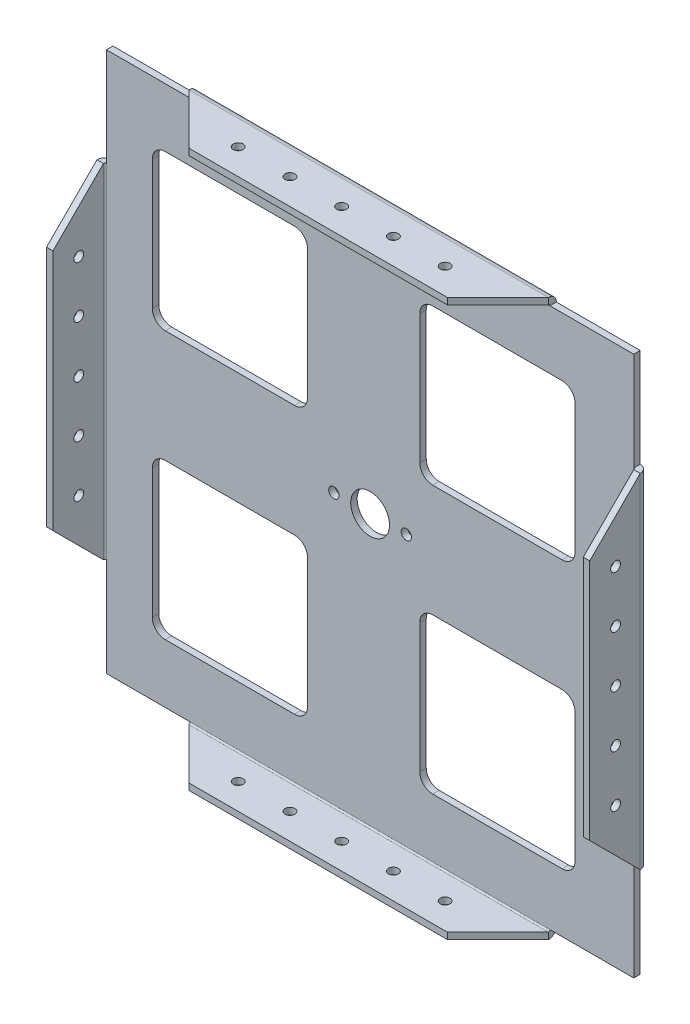
SolidWorks part; units mm, degrees
note: The reader was unsure of these and kept them because the rebuilt part matched: flange length of "Edge-Flange13", "Edge-Flange14", "Edge-Flange15", "Edge-Flange16".
ref_plane "Front Plane" through (0, 0, 0) normal (0, 0, 1) x (1, 0, 0)
ref_plane "Top Plane" through (0, 0, 0) normal (0, 1, 0) x (1, 0, 0)
ref_plane "Right Plane" through (0, 0, 0) normal (1, 0, 0) x (0, 0, -1)
sketch "Sketch1" plane through (0, 0, 0) normal (0, 0, 1) x (1, 0, 0)
  line L1 (-132.2122, 105.5541) -> (134.4878, 105.5541)
  line L2 (-132.2122, 105.5541) -> (-132.2122, -167.4959)
  line L3 (-132.2122, -167.4959) -> (134.4878, -167.4959)
  line L4 (134.4878, 105.5541) -> (134.4878, -167.4959)
  line L5 (-99.4462, 72.7881) -> (-35.9462, 72.7881)
  line L6 (-105.7962, 66.4381) -> (-105.7962, 2.9381)
  line L7 (-99.4462, -3.4119) -> (-35.9462, -3.4119)
  line L8 (-29.5962, 66.4381) -> (-29.5962, 2.9381)
  line L9 (31.8718, 72.7881) -> (95.3718, 72.7881)
  line L10 (25.5218, 66.4381) -> (25.5218, 2.9381)
  line L11 (31.8718, -3.4119) -> (95.3718, -3.4119)
  line L12 (101.7218, 66.4381) -> (101.7218, 2.9381)
  line L13 (-99.4462, -58.5299) -> (-35.9462, -58.5299)
  line L14 (-105.7962, -64.8799) -> (-105.7962, -128.3799)
  line L15 (-99.4462, -134.7299) -> (-35.9462, -134.7299)
  line L16 (-29.5962, -64.8799) -> (-29.5962, -128.3799)
  line L17 (31.8718, -58.5299) -> (95.3718, -58.5299)
  line L18 (25.5218, -64.8799) -> (25.5218, -128.3799)
  line L19 (31.8718, -134.7299) -> (95.3718, -134.7299)
  line L20 (101.7218, -64.8799) -> (101.7218, -128.3799)
  arc A0 (-35.9462, -58.5299) -> (-29.5962, -64.8799) centre (-35.9462, -64.8799) cw
  arc A1 (-29.5962, -128.3799) -> (-35.9462, -134.7299) centre (-35.9462, -128.3799) cw
  arc A2 (-99.4462, -134.7299) -> (-105.7962, -128.3799) centre (-99.4462, -128.3799) cw
  arc A3 (-105.7962, -64.8799) -> (-99.4462, -58.5299) centre (-99.4462, -64.8799) cw
  arc A4 (101.7218, -64.8799) -> (95.3718, -58.5299) centre (95.3718, -64.8799) ccw
  arc A5 (95.3718, -134.7299) -> (101.7218, -128.3799) centre (95.3718, -128.3799) ccw
  arc A6 (31.8718, -134.7299) -> (25.5218, -128.3799) centre (31.8718, -128.3799) cw
  arc A7 (25.5218, -64.8799) -> (31.8718, -58.5299) centre (31.8718, -64.8799) cw
  arc A8 (101.7218, 66.4381) -> (95.3718, 72.7881) centre (95.3718, 66.4381) ccw
  arc A9 (31.8718, -3.4119) -> (25.5218, 2.9381) centre (31.8718, 2.9381) cw
  arc A10 (31.8718, 72.7881) -> (25.5218, 66.4381) centre (31.8718, 66.4381) ccw
  arc A11 (101.7218, 2.9381) -> (95.3718, -3.4119) centre (95.3718, 2.9381) cw
  arc A12 (-29.5962, 2.9381) -> (-35.9462, -3.4119) centre (-35.9462, 2.9381) cw
  arc A13 (-35.9462, 72.7881) -> (-29.5962, 66.4381) centre (-35.9462, 66.4381) cw
  arc A14 (-99.4462, -3.4119) -> (-105.7962, 2.9381) centre (-99.4462, 2.9381) cw
  arc A15 (-105.7962, 66.4381) -> (-99.4462, 72.7881) centre (-99.4462, 66.4381) cw
  circle A16 centre (1.1378, -30.9709) radius 9.525
  circle A17 centre (-16.6422, -30.8439) radius 2.54
  circle A18 centre (18.9174, -30.8439) radius 2.54
  point P24 (-29.5962, -134.7299)
  point P27 (-105.7962, -134.7299)
  point P30 (-105.7962, -58.5299)
  point P33 (101.7218, -58.5299)
  point P36 (101.7218, -134.7299)
  point P39 (25.5218, -134.7299)
  point P44 (101.7218, 72.7881)
  point P49 (25.5218, 72.7881)
  point P52 (101.7218, -3.4119)
  point P57 (-29.5962, 72.7881)
  point P60 (-105.7962, -3.4119)
  point P63 (-105.7962, 72.7881)
  dimension "D19" = 6.35
  dimension "D20" = 19.05
  dimension "D23" = 5.08
  dimension "D24" = 5.08
  dimension "D1" = 266.7
  dimension "D2" = 273.05
  dimension "D3" = 76.2
  dimension "D4" = 76.2
  dimension "D5" = 76.2
  dimension "D6" = 76.2
  dimension "D7" = 76.2
  dimension "D8" = 76.2
  dimension "D9" = 76.2
  dimension "D10" = 76.2
  dimension "D11" = 32.766
  dimension "D12" = 32.766
  dimension "D13" = 32.766
  dimension "D14" = 32.766
  dimension "D15" = 32.766
  dimension "D16" = 32.766
  dimension "D17" = 26.416
  dimension "D18" = 26.416
  dimension "D21" = 136.525
  dimension "D22" = 133.35
  dimension "D25" = 17.78
  dimension "D26" = 17.78
  dimension "D27" = 27.432
  dimension "D28" = 27.432
base flange "Base-Flange4" sketch "Sketch1" thickness 3.175 reverse thickness direction no parameters "D1"=0.7366
edge flange "Edge-Flange13" sketch "Sketch93" flange angle 90 flange length 28.702 flange position material inside bend radius 0.7366 thickness 3.175 relief rectangular parameters "D6"=10
sketch "Sketch93" plane through (0, -167.4959, 0) normal (0, 1, 0) x (-1, 0, 0)
  line L1 (132.2122, 0) -> (-134.4878, 0) construction
  line L2 (-134.4878, 0) -> (-134.4878, 25.527)
  line L3 (-134.4878, 25.527) -> (132.2122, 25.527)
  line L4 (132.2122, 25.527) -> (132.2122, 0)
  line L5 (132.2122, 0) -> (-134.4878, 0)
bend "EdgeBend13" bend radius 0.7366 bend angle 90 parameters "D5"=1
edge flange "Edge-Flange14" sketch "Sketch96" flange angle 90 flange length 28.702 flange position material inside bend radius 0.7366 thickness 3.175 relief rectangular parameters "D6"=10
sketch "Sketch96" plane through (0, 105.5541, 0) normal (0, -1, 0) x (1, 0, 0)
  line L1 (134.4878, 0) -> (-132.2122, 0) construction
  line L2 (-132.2122, 0) -> (-132.2122, 25.527)
  line L3 (-132.2122, 25.527) -> (134.4878, 25.527)
  line L4 (134.4878, 25.527) -> (134.4878, 0)
  line L5 (134.4878, 0) -> (-132.2122, 0)
bend "EdgeBend14" bend radius 0.7366 bend angle 90 parameters "D5"=2
sketch "Sketch97" plane through (0, -164.3209, 0) normal (0, 1, 0) x (1, 0, 0)
  line L0 (-132.2122, -0.7366) -> (134.4878, -0.7366) construction
  line L1 (134.4878, -25.527) -> (90.0378, -25.527)
  line L2 (134.4878, -25.527) -> (134.4878, -0.7366)
  line L3 (134.4878, -0.7366) -> (90.0378, -0.7366)
  line L4 (90.0378, -25.527) -> (90.0378, -0.7366)
  dimension "D1" = 44.45
extrude "Cut-Extrude17" cut sketch "Sketch97" against normal blind 47.752 normal cut yes
sketch "Sketch98" plane through (0, -164.3209, 0) normal (0, 1, 0) x (1, 0, 0)
  line L0 (-132.2122, -0.7366) -> (90.0378, -0.7366) construction
  line L1 (-132.2122, -25.527) -> (-87.7622, -25.527)
  line L2 (-132.2122, -25.527) -> (-132.2122, -0.7366)
  line L3 (-132.2122, -0.7366) -> (-87.7622, -0.7366)
  line L4 (-87.7622, -25.527) -> (-87.7622, -0.7366)
  dimension "D1" = 44.45
extrude "Cut-Extrude18" cut sketch "Sketch98" against normal blind 47.752 normal cut yes
sketch "Sketch99" plane through (0, 105.5541, 0) normal (0, 1, 0) x (1, 0, 0)
  line L0 (134.4878, -0.7366) -> (-132.2122, -0.7366) construction
  line L1 (134.4878, -25.527) -> (90.0378, -25.527)
  line L2 (134.4878, -25.527) -> (134.4878, -0.7366)
  line L3 (134.4878, -0.7366) -> (90.0378, -0.7366)
  line L4 (90.0378, -25.527) -> (90.0378, -0.7366)
  dimension "D1" = 44.45
extrude "Cut-Extrude19" cut sketch "Sketch99" against normal blind 47.752 normal cut yes
sketch "Sketch100" plane through (0, 105.5541, 0) normal (0, 1, 0) x (1, 0, 0)
  line L0 (90.0378, -25.527) -> (-132.2122, -25.527) construction
  line L1 (-132.2122, -0.7366) -> (-87.7622, -0.7366)
  line L2 (-132.2122, -0.7366) -> (-132.2122, -25.527)
  line L3 (-132.2122, -25.527) -> (-87.7622, -25.527)
  line L4 (-87.7622, -0.7366) -> (-87.7622, -25.527)
  dimension "D1" = 44.45
extrude "Cut-Extrude20" cut sketch "Sketch100" against normal blind 47.752 normal cut yes
edge flange "Edge-Flange15" sketch "Sketch103" flange angle 90 flange length 28.702 flange position material inside bend radius 0.7366 thickness 3.175 relief none parameters "D6"=10
sketch "Sketch103" plane through (134.4878, 0, 0) normal (-1, 0, 0) x (0, -1, 0)
  line L1 (163.5843, 0) -> (-101.6425, 0) construction
  line L2 (-101.6425, 0) -> (-101.6425, 25.527)
  line L3 (-101.6425, 25.527) -> (163.5843, 25.527)
  line L4 (163.5843, 25.527) -> (163.5843, 0)
  line L5 (163.5843, 0) -> (-101.6425, 0)
bend "EdgeBend15" bend radius 0.7366 bend angle 90 parameters "D5"=3
edge flange "Edge-Flange16" sketch "Sketch106" flange angle 90 flange length 28.702 flange position material inside bend radius 0.7366 thickness 3.175 relief none parameters "D6"=10
sketch "Sketch106" plane through (-132.2122, 0, 0) normal (1, 0, 0) x (0, 1, 0)
  line L1 (101.6425, 0) -> (-163.5843, 0) construction
  line L2 (-163.5843, 0) -> (-163.5843, 25.527)
  line L3 (-163.5843, 25.527) -> (101.6425, 25.527)
  line L4 (101.6425, 25.527) -> (101.6425, 0)
  line L5 (101.6425, 0) -> (-163.5843, 0)
bend "EdgeBend16" bend radius 0.7366 bend angle 90 parameters "D5"=4
sketch "Sketch107" plane through (-132.2122, 0, 0) normal (-1, 0, 0) x (0, 0, 1)
  line L0 (0.7366, 101.6425) -> (0.7366, -163.5843) construction
  line L1 (25.527, 101.6425) -> (0.7366, 101.6425)
  line L2 (25.527, 101.6425) -> (25.527, 53.8905)
  line L3 (25.527, 53.8905) -> (0.7366, 53.8905)
  line L4 (0.7366, 101.6425) -> (0.7366, 53.8905)
  dimension "D1" = 47.752
extrude "Cut-Extrude21" cut sketch "Sketch107" against normal blind 47.752 normal cut yes
sketch "Sketch108" plane through (-132.2122, 0, 0) normal (-1, 0, 0) x (0, 0, 1)
  line L0 (0.7366, 53.8905) -> (0.7366, -163.5843) construction
  line L1 (25.527, -163.5843) -> (0.7366, -163.5843)
  line L2 (25.527, -163.5843) -> (25.527, -115.8323)
  line L3 (25.527, -115.8323) -> (0.7366, -115.8323)
  line L4 (0.7366, -163.5843) -> (0.7366, -115.8323)
  dimension "D1" = 47.752
extrude "Cut-Extrude22" cut sketch "Sketch108" against normal blind 47.752 normal cut yes
sketch "Sketch109" plane through (134.4878, 0, 0) normal (1, 0, 0) x (0, 0, -1)
  line L0 (-0.7366, -163.5843) -> (-0.7366, 101.6425) construction
  line L1 (-25.527, -163.5843) -> (-0.7366, -163.5843)
  line L2 (-25.527, -163.5843) -> (-25.527, -115.8323)
  line L3 (-25.527, -115.8323) -> (-0.7366, -115.8323)
  line L4 (-0.7366, -163.5843) -> (-0.7366, -115.8323)
  dimension "D1" = 47.752
extrude "Cut-Extrude23" cut sketch "Sketch109" against normal blind 47.752 normal cut yes
sketch "Sketch110" plane through (134.4878, 0, 0) normal (1, 0, 0) x (0, 0, -1)
  line L0 (-0.7366, -115.8323) -> (-0.7366, 101.6425) construction
  line L1 (-25.527, 101.6425) -> (-0.7366, 101.6425)
  line L2 (-25.527, 101.6425) -> (-25.527, 53.8905)
  line L3 (-25.527, 53.8905) -> (-0.7366, 53.8905)
  line L4 (-0.7366, 101.6425) -> (-0.7366, 53.8905)
  dimension "D1" = 47.752
extrude "Cut-Extrude24" cut sketch "Sketch110" against normal blind 47.752 normal cut yes
chamfer "Chamfer5" distance 25.4 angle 45 8 edges at (90.0378, -165.9084, 25.527) (132.9003, -115.8323, 25.527) (-87.7622, -165.9084, 25.527) (-130.6247, -115.8323, 25.527) (-130.6247, 53.8905, 25.527) (-87.7622, 103.9666, 25.527) (132.9003, 53.8905, 25.527) (90.0378, 103.9666, 25.527)
sketch "Sketch113" plane through (0, 105.5541, 0) normal (0, 1, 0) x (1, 0, 0)
  line L0 (64.6378, -25.527) -> (-62.3622, -25.527) construction
  circle A0 centre (50.8, -12.827) radius 2.413
  circle A1 centre (25.4, -12.827) radius 2.413
  circle A2 centre (0, -12.827) radius 2.413
  circle A3 centre (-25.4, -12.827) radius 2.413
  circle A4 centre (-50.8, -12.827) radius 2.413
  dimension "D1" = 4.826
  dimension "D2" = 4.826
  dimension "D3" = 4.826
  dimension "D4" = 4.826
  dimension "D5" = 4.826
  dimension "D6" = 12.7
  dimension "D7" = 25.4
  dimension "D8" = 25.4
  dimension "D9" = 25.4
  dimension "D10" = 25.4
extrude "Cut-Extrude25" cut sketch "Sketch113" against normal through all normal cut yes
sketch "Sketch114" plane through (134.4878, 0, 0) normal (1, 0, 0) x (0, 0, -1)
  line L1 (-25.527, -90.4323) -> (-25.527, 28.4905) construction
  circle A0 centre (-12.827, -81.8471) radius 2.413
  circle A1 centre (-12.827, -56.4471) radius 2.413
  circle A2 centre (-12.827, -31.0471) radius 2.413
  circle A3 centre (-12.827, -5.6471) radius 2.413
  circle A4 centre (-12.827, 19.7529) radius 2.413
  point P10 (-25.527, -30.9709)
  dimension "D1" = 4.826
  dimension "D2" = 4.826
  dimension "D3" = 4.826
  dimension "D4" = 4.826
  dimension "D5" = 4.826
  dimension "D6" = 136.4488
  dimension "D7" = 25.4
  dimension "D8" = 25.4
  dimension "D9" = 25.4
  dimension "D10" = 25.4
  dimension "D11" = 12.7
extrude "Cut-Extrude26" cut sketch "Sketch114" against normal through all normal cut yes
sketch "Sketch115" plane through (134.4878, 0, 0) normal (1, 0, 0) x (0, 0, -1)
  line L0 (-0.7366, -167.4959) -> (-0.7366, -164.3209)
  line L1 (0, -163.5843) -> (3.175, -163.5843)
  arc A0 (-0.7366, -167.4959) -> (3.175, -163.5843) centre (-0.7366, -163.5843) ccw
  arc A1 (-0.7366, -164.3209) -> (0, -163.5843) centre (-0.7366, -163.5843) ccw
extrude "Cut-Extrude28" cut sketch "Sketch115" against normal blind 45.0596 normal cut yes
sketch "Sketch116" plane through (-132.2122, 0, 0) normal (-1, 0, 0) x (0, 0, 1)
  line L0 (0, -163.5843) -> (-3.175, -163.5843)
  line L1 (0.7366, -164.3209) -> (0.7366, -167.4959)
  arc A0 (0, -163.5843) -> (0.7366, -164.3209) centre (0.7366, -163.5843) ccw
  arc A1 (-3.175, -163.5843) -> (0.7366, -167.4959) centre (0.7366, -163.5843) ccw
extrude "Cut-Extrude29" cut sketch "Sketch116" against normal blind 45.0596 normal cut yes
sketch "Sketch117" plane through (0, -163.5843, 0) normal (0, -1, 0) x (1, 0, 0)
  line L0 (-129.0372, 0.7366) -> (-132.2122, 0.7366)
  line L1 (-128.3006, 0) -> (-128.3006, -3.175)
  arc A0 (-132.2122, 0.7366) -> (-128.3006, -3.175) centre (-128.3006, 0.7366) ccw
  arc A1 (-129.0372, 0.7366) -> (-128.3006, 0) centre (-128.3006, 0.7366) ccw
extrude "Cut-Extrude30" cut sketch "Sketch117" against normal blind 48.3616 normal cut yes
sketch "Sketch118" plane through (134.4878, 0, 0) normal (1, 0, 0) x (0, 0, -1)
  line L0 (-0.7366, 102.3791) -> (-0.7366, 105.5541)
  line L1 (0, 101.6425) -> (3.175, 101.6425)
  arc A0 (0, 101.6425) -> (-0.7366, 102.3791) centre (-0.7366, 101.6425) ccw
  arc A1 (3.175, 101.6425) -> (-0.7366, 105.5541) centre (-0.7366, 101.6425) ccw
extrude "Cut-Extrude31" cut sketch "Sketch118" against normal blind 45.0596 normal cut yes
sketch "Sketch119" plane through (-132.2122, 0, 0) normal (-1, 0, 0) x (0, 0, 1)
  line L0 (0.7366, 102.3791) -> (0.7366, 105.5541)
  line L1 (0, 101.6425) -> (-3.175, 101.6425)
  arc A0 (0.7366, 102.3791) -> (0, 101.6425) centre (0.7366, 101.6425) ccw
  arc A1 (0.7366, 105.5541) -> (-3.175, 101.6425) centre (0.7366, 101.6425) ccw
extrude "Cut-Extrude32" cut sketch "Sketch119" against normal blind 45.0596 normal cut yes
sketch "Sketch120" plane through (0, 101.6425, 0) normal (0, 1, 0) x (1, 0, 0)
  line L0 (-129.0372, -0.7366) -> (-132.2122, -0.7366)
  line L1 (-128.3006, 0) -> (-128.3006, 3.175)
  arc A0 (-128.3006, 0) -> (-129.0372, -0.7366) centre (-128.3006, -0.7366) ccw
  arc A1 (-128.3006, 3.175) -> (-132.2122, -0.7366) centre (-128.3006, -0.7366) ccw
extrude "Cut-Extrude33" cut sketch "Sketch120" against normal blind 48.3616 normal cut yes
sketch "Sketch121" plane through (0, -163.5843, 0) normal (0, -1, 0) x (1, 0, 0)
  line L0 (131.3128, 0.7366) -> (134.4878, 0.7366)
  line L1 (130.5762, 0) -> (130.5762, -3.175)
  arc A0 (130.5762, 0) -> (131.3128, 0.7366) centre (130.5762, 0.7366) ccw
  arc A1 (130.5762, -3.175) -> (134.4878, 0.7366) centre (130.5762, 0.7366) ccw
extrude "Cut-Extrude34" cut sketch "Sketch121" against normal blind 48.3616 normal cut yes
sketch "Sketch122" plane through (0, 101.6425, 0) normal (0, 1, 0) x (1, 0, 0)
  line L0 (134.4878, -0.7366) -> (131.3128, -0.7366)
  line L1 (130.5762, 0) -> (130.5762, 3.175)
  arc A0 (131.3128, -0.7366) -> (130.5762, 0) centre (130.5762, -0.7366) ccw
  arc A1 (134.4878, -0.7366) -> (130.5762, 3.175) centre (130.5762, -0.7366) ccw
extrude "Cut-Extrude35" cut sketch "Sketch122" against normal blind 48.3616 normal cut yes
sketch "Bend-Lines7" [suppressed] plane through (0, 0, 0) normal (0, 1, 0) x (1, 0, 0)
sketch "Bounding-Box7" [suppressed] plane through (0, 0, 0) normal (0, 1, 0) x (1, 0, 0)
sheet metal parameters "Sheet-Metal4" thickness 3.175 parameters "D1"=0.7366
flat pattern "Flat-Pattern4" [suppressed]
sketch "Bend-Lines8" plane through (0, 0, 0) normal (0, 1, 0) x (1, 0, 0)
sketch3d "Bounding-Box8" [suppressed]
  line L0 (134.4878, 105.5541, 0) -> (134.4878, -167.4959, 0) construction
  line L1 (-132.2122, 105.5541, 0) -> (-132.2122, -167.4959, 0) construction
  line L2 (134.4878, 105.5541, 0) -> (-132.2122, 105.5541, 0) construction
  line L3 (134.4878, -167.4959, 0) -> (-132.2122, -167.4959, 0) construction
sheet metal parameters "Sheet-Metal32" thickness 3.175 parameters "D1"=0.7366
flat pattern "Flat-Pattern4"
sketch "Bend-Lines8" plane through (0, 0, 0) normal (0, 0, 1) x (1, 0, 0)
  line L0 (-132.2122, -164.9857) -> (134.4878, -164.9857) construction
  line L1 (-132.2122, -164.9857) -> (134.4878, -164.9857) construction
sketch3d "Bounding-Box8" [suppressed]
  line L0 (134.4878, 105.5541, 0) -> (134.4878, -191.1776, 0) construction
  line L1 (-132.2122, 105.5541, 0) -> (-132.2122, -191.1776, 0) construction
  line L2 (134.4878, 105.5541, 0) -> (-132.2122, 105.5541, 0) construction
  line L3 (134.4878, -191.1776, 0) -> (-132.2122, -191.1776, 0) construction
bend of the flat pattern "Flatten-<EdgeBend13>1"
sheet metal parameters "Sheet-Metal33" thickness 3.175 parameters "D1"=0.7366
flat pattern "Flat-Pattern4"
sketch "Bend-Lines8" plane through (0, 0, 0) normal (0, 0, 1) x (1, 0, 0)
  line L0 (-132.2122, -164.9857) -> (134.4878, -164.9857) construction
  line L1 (-132.2122, -164.9857) -> (134.4878, -164.9857) construction
  line L2 (134.4878, 103.0439) -> (-132.2122, 103.0439) construction
  line L3 (134.4878, 103.0439) -> (-132.2122, 103.0439) construction
sketch3d "Bounding-Box8" [suppressed]
  line L0 (134.4878, 129.2357, 0) -> (134.4878, -191.1776, 0) construction
  line L1 (-132.2122, 129.2357, 0) -> (-132.2122, -191.1776, 0) construction
  line L2 (134.4878, 129.2357, 0) -> (-132.2122, 129.2357, 0) construction
  line L3 (134.4878, -191.1776, 0) -> (-132.2122, -191.1776, 0) construction
bend of the flat pattern "Flatten-<EdgeBend13>1"
bend of the flat pattern "Flatten-<EdgeBend14>1"
sheet metal parameters "Sheet-Metal34" thickness 3.175 parameters "D1"=0.7366
flat pattern "Flat-Pattern4"
sketch "Bend-Lines8" plane through (0, 0, 0) normal (0, 0, 1) x (1, 0, 0)
  line L0 (134.4878, -164.9857) -> (-132.2122, -164.9857) construction
  line L1 (134.4878, -164.9857) -> (-132.2122, -164.9857) construction
  line L2 (134.4878, 103.0439) -> (-132.2122, 103.0439) construction
  line L3 (134.4878, 103.0439) -> (-132.2122, 103.0439) construction
sketch3d "Bounding-Box8" [suppressed]
  line L0 (134.4878, 129.2357, 0) -> (134.4878, -191.1776, 0) construction
  line L1 (-132.2122, 129.2357, 0) -> (-132.2122, -191.1776, 0) construction
  line L2 (134.4878, 129.2357, 0) -> (-132.2122, 129.2357, 0) construction
  line L3 (134.4878, -191.1776, 0) -> (-132.2122, -191.1776, 0) construction
bend of the flat pattern "Flatten-<EdgeBend13>1"
bend of the flat pattern "Flatten-<EdgeBend14>1"
sheet metal parameters "Sheet-Metal35" thickness 3.175 parameters "D1"=0.7366
flat pattern "Flat-Pattern4"
sketch "Bend-Lines8" plane through (0, 0, 0) normal (0, 0, 1) x (1, 0, 0)
  line L0 (134.4878, -164.9857) -> (-132.2122, -164.9857) construction
  line L1 (134.4878, -164.9857) -> (-132.2122, -164.9857) construction
  line L2 (134.4878, 103.0439) -> (-132.2122, 103.0439) construction
  line L3 (134.4878, 103.0439) -> (-132.2122, 103.0439) construction
sketch3d "Bounding-Box8" [suppressed]
  line L0 (134.4878, 129.2357, 0) -> (134.4878, -191.1776, 0) construction
  line L1 (-132.2122, 129.2357, 0) -> (-132.2122, -191.1776, 0) construction
  line L2 (134.4878, 129.2357, 0) -> (-132.2122, 129.2357, 0) construction
  line L3 (134.4878, -191.1776, 0) -> (-132.2122, -191.1776, 0) construction
bend of the flat pattern "Flatten-<EdgeBend13>1"
bend of the flat pattern "Flatten-<EdgeBend14>1"
sheet metal parameters "Sheet-Metal36" thickness 3.175 parameters "D1"=0.7366
flat pattern "Flat-Pattern4"
sketch "Bend-Lines8" plane through (0, 0, 0) normal (0, 0, 1) x (1, 0, 0)
  line L0 (134.4878, -164.9857) -> (-132.2122, -164.9857) construction
  line L1 (134.4878, -164.9857) -> (-132.2122, -164.9857) construction
  line L2 (134.4878, 103.0439) -> (-132.2122, 103.0439) construction
  line L3 (134.4878, 103.0439) -> (-132.2122, 103.0439) construction
sketch3d "Bounding-Box8" [suppressed]
  line L0 (134.4878, 129.2357, 0) -> (134.4878, -191.1776, 0) construction
  line L1 (-132.2122, 129.2357, 0) -> (-132.2122, -191.1776, 0) construction
  line L2 (134.4878, 129.2357, 0) -> (-132.2122, 129.2357, 0) construction
  line L3 (134.4878, -191.1776, 0) -> (-132.2122, -191.1776, 0) construction
bend of the flat pattern "Flatten-<EdgeBend13>1"
bend of the flat pattern "Flatten-<EdgeBend14>1"
sheet metal parameters "Sheet-Metal37" thickness 3.175 parameters "D1"=0.7366
flat pattern "Flat-Pattern4"
sketch "Bend-Lines8" plane through (0, 0, 0) normal (0, 0, 1) x (1, 0, 0)
  line L0 (134.4878, -164.9857) -> (-132.2122, -164.9857) construction
  line L1 (134.4878, -164.9857) -> (-132.2122, -164.9857) construction
  line L2 (-132.2122, 103.0439) -> (134.4878, 103.0439) construction
  line L3 (-132.2122, 103.0439) -> (134.4878, 103.0439) construction
sketch3d "Bounding-Box8" [suppressed]
  line L0 (134.4878, 129.2357, 0) -> (134.4878, -191.1776, 0) construction
  line L1 (-132.2122, 129.2357, 0) -> (-132.2122, -191.1776, 0) construction
  line L2 (134.4878, 129.2357, 0) -> (-132.2122, 129.2357, 0) construction
  line L3 (134.4878, -191.1776, 0) -> (-132.2122, -191.1776, 0) construction
bend of the flat pattern "Flatten-<EdgeBend13>1"
bend of the flat pattern "Flatten-<EdgeBend14>1"
sheet metal parameters "Sheet-Metal38" thickness 3.175 parameters "D1"=0.7366
flat pattern "Flat-Pattern4"
sketch "Bend-Lines8" plane through (0, 0, 0) normal (0, 0, 1) x (1, 0, 0)
  line L0 (134.4878, -164.9857) -> (-132.2122, -164.9857) construction
  line L1 (134.4878, -164.9857) -> (-132.2122, -164.9857) construction
  line L2 (-132.2122, 103.0439) -> (134.4878, 103.0439) construction
  line L3 (-132.2122, 103.0439) -> (134.4878, 103.0439) construction
  line L4 (131.9776, -163.5843) -> (131.9776, 101.6425) construction
  line L5 (131.9776, -163.5843) -> (131.9776, 101.6425) construction
sketch3d "Bounding-Box8" [suppressed]
  line L0 (158.1695, 129.2357, 0) -> (158.1695, -191.1776, 0) construction
  line L1 (-132.2122, 129.2357, 0) -> (-132.2122, -191.1776, 0) construction
  line L2 (158.1695, 129.2357, 0) -> (-132.2122, 129.2357, 0) construction
  line L3 (158.1695, -191.1776, 0) -> (-132.2122, -191.1776, 0) construction
bend of the flat pattern "Flatten-<EdgeBend13>1"
bend of the flat pattern "Flatten-<EdgeBend14>1"
bend of the flat pattern "Flatten-<EdgeBend15>1"
sheet metal parameters "Sheet-Metal39" thickness 3.175 parameters "D1"=0.7366
flat pattern "Flat-Pattern4"
sketch "Bend-Lines8" plane through (0, 0, 0) normal (0, 0, 1) x (1, 0, 0)
  line L0 (134.4878, -164.9857) -> (-132.2122, -164.9857) construction
  line L1 (134.4878, -164.9857) -> (-132.2122, -164.9857) construction
  line L2 (-132.2122, 103.0439) -> (134.4878, 103.0439) construction
  line L3 (-132.2122, 103.0439) -> (134.4878, 103.0439) construction
  line L4 (131.9776, -163.5843) -> (131.9776, 101.6425) construction
  line L5 (131.9776, -163.5843) -> (131.9776, 101.6425) construction
  line L6 (-129.702, 101.6425) -> (-129.702, -163.5843) construction
  line L7 (-129.702, 101.6425) -> (-129.702, -163.5843) construction
sketch3d "Bounding-Box8" [suppressed]
  line L0 (158.1695, 129.2357, 0) -> (158.1695, -191.1776, 0) construction
  line L1 (-155.8938, 129.2357, 0) -> (-155.8938, -191.1776, 0) construction
  line L2 (158.1695, 129.2357, 0) -> (-155.8938, 129.2357, 0) construction
  line L3 (158.1695, -191.1776, 0) -> (-155.8938, -191.1776, 0) construction
bend of the flat pattern "Flatten-<EdgeBend13>1"
bend of the flat pattern "Flatten-<EdgeBend14>1"
bend of the flat pattern "Flatten-<EdgeBend15>1"
bend of the flat pattern "Flatten-<EdgeBend16>1"
sheet metal parameters "Sheet-Metal40" thickness 3.175 parameters "D1"=0.7366
flat pattern "Flat-Pattern4"
sketch "Bend-Lines8" plane through (0, 0, 0) normal (0, 0, 1) x (1, 0, 0)
  line L0 (134.4878, -164.9857) -> (-132.2122, -164.9857) construction
  line L1 (134.4878, -164.9857) -> (-132.2122, -164.9857) construction
  line L2 (-132.2122, 103.0439) -> (134.4878, 103.0439) construction
  line L3 (-132.2122, 103.0439) -> (134.4878, 103.0439) construction
  line L4 (131.9776, -163.5843) -> (131.9776, 101.6425) construction
  line L5 (131.9776, -163.5843) -> (131.9776, 101.6425) construction
  line L6 (-129.702, 101.6425) -> (-129.702, -163.5843) construction
  line L7 (-129.702, 101.6425) -> (-129.702, -163.5843) construction
sketch3d "Bounding-Box8" [suppressed]
  line L0 (158.1695, 129.2357, 0) -> (158.1695, -191.1776, 0) construction
  line L1 (-155.8938, 129.2357, 0) -> (-155.8938, -191.1776, 0) construction
  line L2 (158.1695, 129.2357, 0) -> (-155.8938, 129.2357, 0) construction
  line L3 (158.1695, -191.1776, 0) -> (-155.8938, -191.1776, 0) construction
bend of the flat pattern "Flatten-<EdgeBend13>1"
bend of the flat pattern "Flatten-<EdgeBend14>1"
bend of the flat pattern "Flatten-<EdgeBend15>1"
bend of the flat pattern "Flatten-<EdgeBend16>1"
sheet metal parameters "Sheet-Metal41" thickness 3.175 parameters "D1"=0.7366
flat pattern "Flat-Pattern4"
sketch "Bend-Lines8" plane through (0, 0, 0) normal (0, 0, 1) x (1, 0, 0)
  line L0 (134.4878, -164.9857) -> (-132.2122, -164.9857) construction
  line L1 (134.4878, -164.9857) -> (-132.2122, -164.9857) construction
  line L2 (-132.2122, 103.0439) -> (134.4878, 103.0439) construction
  line L3 (-132.2122, 103.0439) -> (134.4878, 103.0439) construction
  line L4 (131.9776, -163.5843) -> (131.9776, 101.6425) construction
  line L5 (131.9776, -163.5843) -> (131.9776, 101.6425) construction
  line L6 (-129.702, -163.5843) -> (-129.702, 101.6425) construction
  line L7 (-129.702, -163.5843) -> (-129.702, 101.6425) construction
sketch3d "Bounding-Box8" [suppressed]
  line L0 (158.1695, 129.2357, 0) -> (158.1695, -191.1776, 0) construction
  line L1 (-155.8938, 129.2357, 0) -> (-155.8938, -191.1776, 0) construction
  line L2 (158.1695, 129.2357, 0) -> (-155.8938, 129.2357, 0) construction
  line L3 (158.1695, -191.1776, 0) -> (-155.8938, -191.1776, 0) construction
bend of the flat pattern "Flatten-<EdgeBend13>1"
bend of the flat pattern "Flatten-<EdgeBend14>1"
bend of the flat pattern "Flatten-<EdgeBend15>1"
bend of the flat pattern "Flatten-<EdgeBend16>1"
sheet metal parameters "Sheet-Metal42" thickness 3.175 parameters "D1"=0.7366
flat pattern "Flat-Pattern4"
sketch "Bend-Lines8" plane through (0, 0, 0) normal (0, 0, 1) x (1, 0, 0)
  line L0 (134.4878, -164.9857) -> (-132.2122, -164.9857) construction
  line L1 (134.4878, -164.9857) -> (-132.2122, -164.9857) construction
  line L2 (-132.2122, 103.0439) -> (134.4878, 103.0439) construction
  line L3 (-132.2122, 103.0439) -> (134.4878, 103.0439) construction
  line L4 (131.9776, -163.5843) -> (131.9776, 101.6425) construction
  line L5 (131.9776, -163.5843) -> (131.9776, 101.6425) construction
  line L6 (-129.702, -163.5843) -> (-129.702, 101.6425) construction
  line L7 (-129.702, -163.5843) -> (-129.702, 101.6425) construction
sketch3d "Bounding-Box8" [suppressed]
  line L0 (158.1695, 129.2357, 0) -> (158.1695, -191.1776, 0) construction
  line L1 (-155.8938, 129.2357, 0) -> (-155.8938, -191.1776, 0) construction
  line L2 (158.1695, 129.2357, 0) -> (-155.8938, 129.2357, 0) construction
  line L3 (158.1695, -191.1776, 0) -> (-155.8938, -191.1776, 0) construction
bend of the flat pattern "Flatten-<EdgeBend13>1"
bend of the flat pattern "Flatten-<EdgeBend14>1"
bend of the flat pattern "Flatten-<EdgeBend15>1"
bend of the flat pattern "Flatten-<EdgeBend16>1"
sheet metal parameters "Sheet-Metal43" thickness 3.175 parameters "D1"=0.7366
flat pattern "Flat-Pattern4"
sketch "Bend-Lines8" plane through (0, 0, 0) normal (0, 0, 1) x (1, 0, 0)
  line L0 (134.4878, -164.9857) -> (-132.2122, -164.9857) construction
  line L1 (134.4878, -164.9857) -> (-132.2122, -164.9857) construction
  line L2 (-132.2122, 103.0439) -> (134.4878, 103.0439) construction
  line L3 (-132.2122, 103.0439) -> (134.4878, 103.0439) construction
  line L4 (131.9776, 101.6425) -> (131.9776, -163.5843) construction
  line L5 (131.9776, 101.6425) -> (131.9776, -163.5843) construction
  line L6 (-129.702, -163.5843) -> (-129.702, 101.6425) construction
  line L7 (-129.702, -163.5843) -> (-129.702, 101.6425) construction
sketch3d "Bounding-Box8" [suppressed]
  line L0 (158.1695, 129.2357, 0) -> (158.1695, -191.1776, 0) construction
  line L1 (-155.8938, 129.2357, 0) -> (-155.8938, -191.1776, 0) construction
  line L2 (158.1695, 129.2357, 0) -> (-155.8938, 129.2357, 0) construction
  line L3 (158.1695, -191.1776, 0) -> (-155.8938, -191.1776, 0) construction
bend of the flat pattern "Flatten-<EdgeBend13>1"
bend of the flat pattern "Flatten-<EdgeBend14>1"
bend of the flat pattern "Flatten-<EdgeBend15>1"
bend of the flat pattern "Flatten-<EdgeBend16>1"
sheet metal parameters "Sheet-Metal44" thickness 3.175 parameters "D1"=0.7366
flat pattern "Flat-Pattern4"
sketch "Bend-Lines8" plane through (0, 0, 0) normal (0, 0, 1) x (1, 0, 0)
  line L0 (134.4878, -164.9857) -> (-132.2122, -164.9857) construction
  line L1 (134.4878, -164.9857) -> (-132.2122, -164.9857) construction
  line L2 (-132.2122, 103.0439) -> (134.4878, 103.0439) construction
  line L3 (-132.2122, 103.0439) -> (134.4878, 103.0439) construction
  line L4 (131.9776, 101.6425) -> (131.9776, -163.5843) construction
  line L5 (131.9776, 101.6425) -> (131.9776, -163.5843) construction
  line L6 (-129.702, -163.5843) -> (-129.702, 101.6425) construction
  line L7 (-129.702, -163.5843) -> (-129.702, 101.6425) construction
sketch3d "Bounding-Box8" [suppressed]
  line L0 (158.1695, 129.2357, 0) -> (158.1695, -191.1776, 0) construction
  line L1 (-155.8938, 129.2357, 0) -> (-155.8938, -191.1776, 0) construction
  line L2 (158.1695, 129.2357, 0) -> (-155.8938, 129.2357, 0) construction
  line L3 (158.1695, -191.1776, 0) -> (-155.8938, -191.1776, 0) construction
bend of the flat pattern "Flatten-<EdgeBend13>1"
bend of the flat pattern "Flatten-<EdgeBend14>1"
bend of the flat pattern "Flatten-<EdgeBend15>1"
bend of the flat pattern "Flatten-<EdgeBend16>1"
sheet metal parameters "Sheet-Metal45" thickness 3.175 parameters "D1"=0.7366
flat pattern "Flat-Pattern4"
sketch "Bend-Lines8" plane through (0, 0, 0) normal (0, 0, 1) x (1, 0, 0)
  line L0 (134.4878, -164.9857) -> (-132.2122, -164.9857) construction
  line L1 (134.4878, -164.9857) -> (-132.2122, -164.9857) construction
  line L2 (-132.2122, 103.0439) -> (134.4878, 103.0439) construction
  line L3 (-132.2122, 103.0439) -> (134.4878, 103.0439) construction
  line L4 (131.9776, 101.6425) -> (131.9776, -163.5843) construction
  line L5 (131.9776, 101.6425) -> (131.9776, -163.5843) construction
  line L6 (-129.702, -163.5843) -> (-129.702, 101.6425) construction
  line L7 (-129.702, -163.5843) -> (-129.702, 101.6425) construction
sketch3d "Bounding-Box8" [suppressed]
  line L0 (158.1695, 129.2357, 0) -> (158.1695, -191.1776, 0) construction
  line L1 (-155.8938, 129.2357, 0) -> (-155.8938, -191.1776, 0) construction
  line L2 (158.1695, 129.2357, 0) -> (-155.8938, 129.2357, 0) construction
  line L3 (158.1695, -191.1776, 0) -> (-155.8938, -191.1776, 0) construction
bend of the flat pattern "Flatten-<EdgeBend13>1"
bend of the flat pattern "Flatten-<EdgeBend14>1"
bend of the flat pattern "Flatten-<EdgeBend15>1"
bend of the flat pattern "Flatten-<EdgeBend16>1"
sheet metal parameters "Sheet-Metal47" thickness 3.175 parameters "D1"=0.7366
flat pattern "Flat-Pattern4"
sketch "Bend-Lines8" plane through (0, 0, 0) normal (0, 0, 1) x (1, 0, 0)
  line L0 (-132.2122, -164.9857) -> (89.4282, -164.9857) construction
  line L1 (-132.2122, -164.9857) -> (89.4282, -164.9857) construction
  line L2 (-132.2122, 103.0439) -> (134.4878, 103.0439) construction
  line L3 (-132.2122, 103.0439) -> (134.4878, 103.0439) construction
  line L4 (131.9776, 101.6425) -> (131.9776, -163.5843) construction
  line L5 (131.9776, 101.6425) -> (131.9776, -163.5843) construction
  line L6 (-129.702, -163.5843) -> (-129.702, 101.6425) construction
  line L7 (-129.702, -163.5843) -> (-129.702, 101.6425) construction
sketch3d "Bounding-Box8" [suppressed]
  line L0 (158.1695, 129.2357, 0) -> (158.1695, -191.1776, 0) construction
  line L1 (-155.8938, 129.2357, 0) -> (-155.8938, -191.1776, 0) construction
  line L2 (158.1695, 129.2357, 0) -> (-155.8938, 129.2357, 0) construction
  line L3 (158.1695, -191.1776, 0) -> (-155.8938, -191.1776, 0) construction
bend of the flat pattern "Flatten-<EdgeBend13>1"
bend of the flat pattern "Flatten-<EdgeBend14>1"
bend of the flat pattern "Flatten-<EdgeBend15>1"
bend of the flat pattern "Flatten-<EdgeBend16>1"
sheet metal parameters "Sheet-Metal48" thickness 3.175 parameters "D1"=0.7366
flat pattern "Flat-Pattern4"
sketch "Bend-Lines8" plane through (0, 0, 0) normal (0, 0, 1) x (1, 0, 0)
  line L0 (-87.1526, -164.9857) -> (89.4282, -164.9857) construction
  line L1 (-87.1526, -164.9857) -> (89.4282, -164.9857) construction
  line L2 (-132.2122, 103.0439) -> (134.4878, 103.0439) construction
  line L3 (-132.2122, 103.0439) -> (134.4878, 103.0439) construction
  line L4 (131.9776, 101.6425) -> (131.9776, -163.5843) construction
  line L5 (131.9776, 101.6425) -> (131.9776, -163.5843) construction
  line L6 (-129.702, -163.5843) -> (-129.702, 101.6425) construction
  line L7 (-129.702, -163.5843) -> (-129.702, 101.6425) construction
sketch3d "Bounding-Box8" [suppressed]
  line L0 (158.1695, 129.2357, 0) -> (158.1695, -191.1776, 0) construction
  line L1 (-155.8938, 129.2357, 0) -> (-155.8938, -191.1776, 0) construction
  line L2 (158.1695, 129.2357, 0) -> (-155.8938, 129.2357, 0) construction
  line L3 (158.1695, -191.1776, 0) -> (-155.8938, -191.1776, 0) construction
bend of the flat pattern "Flatten-<EdgeBend13>1"
bend of the flat pattern "Flatten-<EdgeBend14>1"
bend of the flat pattern "Flatten-<EdgeBend15>1"
bend of the flat pattern "Flatten-<EdgeBend16>1"
sheet metal parameters "Sheet-Metal49" thickness 3.175 parameters "D1"=0.7366
flat pattern "Flat-Pattern4"
sketch "Bend-Lines8" plane through (0, 0, 0) normal (0, 0, 1) x (1, 0, 0)
  line L0 (-87.1526, -164.9857) -> (89.4282, -164.9857) construction
  line L1 (-87.1526, -164.9857) -> (89.4282, -164.9857) construction
  line L2 (-132.2122, 103.0439) -> (134.4878, 103.0439) construction
  line L3 (-132.2122, 103.0439) -> (134.4878, 103.0439) construction
  line L4 (131.9776, 101.6425) -> (131.9776, -163.5843) construction
  line L5 (131.9776, 101.6425) -> (131.9776, -163.5843) construction
  line L6 (-129.702, 101.6425) -> (-129.702, -115.2227) construction
  line L7 (-129.702, 101.6425) -> (-129.702, -115.2227) construction
sketch3d "Bounding-Box8" [suppressed]
  line L0 (158.1695, 129.2357, 0) -> (158.1695, -191.1776, 0) construction
  line L1 (-155.8938, 129.2357, 0) -> (-155.8938, -191.1776, 0) construction
  line L2 (158.1695, 129.2357, 0) -> (-155.8938, 129.2357, 0) construction
  line L3 (158.1695, -191.1776, 0) -> (-155.8938, -191.1776, 0) construction
bend of the flat pattern "Flatten-<EdgeBend13>1"
bend of the flat pattern "Flatten-<EdgeBend14>1"
bend of the flat pattern "Flatten-<EdgeBend15>1"
bend of the flat pattern "Flatten-<EdgeBend16>1"
sheet metal parameters "Sheet-Metal50" thickness 3.175 parameters "D1"=0.7366
flat pattern "Flat-Pattern4"
sketch "Bend-Lines8" plane through (0, 0, 0) normal (0, 0, 1) x (1, 0, 0)
  line L0 (-87.1526, -164.9857) -> (89.4282, -164.9857) construction
  line L1 (-87.1526, -164.9857) -> (89.4282, -164.9857) construction
  line L2 (-132.2122, 103.0439) -> (89.4282, 103.0439) construction
  line L3 (-132.2122, 103.0439) -> (89.4282, 103.0439) construction
  line L4 (131.9776, 101.6425) -> (131.9776, -163.5843) construction
  line L5 (131.9776, 101.6425) -> (131.9776, -163.5843) construction
  line L6 (-129.702, 101.6425) -> (-129.702, -115.2227) construction
  line L7 (-129.702, 101.6425) -> (-129.702, -115.2227) construction
sketch3d "Bounding-Box8" [suppressed]
  line L0 (158.1695, 129.2357, 0) -> (158.1695, -191.1776, 0) construction
  line L1 (-155.8938, 129.2357, 0) -> (-155.8938, -191.1776, 0) construction
  line L2 (158.1695, 129.2357, 0) -> (-155.8938, 129.2357, 0) construction
  line L3 (158.1695, -191.1776, 0) -> (-155.8938, -191.1776, 0) construction
bend of the flat pattern "Flatten-<EdgeBend13>1"
bend of the flat pattern "Flatten-<EdgeBend14>1"
bend of the flat pattern "Flatten-<EdgeBend15>1"
bend of the flat pattern "Flatten-<EdgeBend16>1"
sheet metal parameters "Sheet-Metal51" thickness 3.175 parameters "D1"=0.7366
flat pattern "Flat-Pattern4"
sketch "Bend-Lines8" plane through (0, 0, 0) normal (0, 0, 1) x (1, 0, 0)
  line L0 (-87.1526, -164.9857) -> (89.4282, -164.9857) construction
  line L1 (-87.1526, -164.9857) -> (89.4282, -164.9857) construction
  line L2 (89.4282, 103.0439) -> (-87.1526, 103.0439) construction
  line L3 (89.4282, 103.0439) -> (-87.1526, 103.0439) construction
  line L4 (131.9776, 101.6425) -> (131.9776, -163.5843) construction
  line L5 (131.9776, 101.6425) -> (131.9776, -163.5843) construction
  line L6 (-129.702, 101.6425) -> (-129.702, -115.2227) construction
  line L7 (-129.702, 101.6425) -> (-129.702, -115.2227) construction
sketch3d "Bounding-Box8" [suppressed]
  line L0 (158.1695, 129.2357, 0) -> (158.1695, -191.1776, 0) construction
  line L1 (-155.8938, 129.2357, 0) -> (-155.8938, -191.1776, 0) construction
  line L2 (158.1695, 129.2357, 0) -> (-155.8938, 129.2357, 0) construction
  line L3 (158.1695, -191.1776, 0) -> (-155.8938, -191.1776, 0) construction
bend of the flat pattern "Flatten-<EdgeBend13>1"
bend of the flat pattern "Flatten-<EdgeBend14>1"
bend of the flat pattern "Flatten-<EdgeBend15>1"
bend of the flat pattern "Flatten-<EdgeBend16>1"
sheet metal parameters "Sheet-Metal52" thickness 3.175 parameters "D1"=0.7366
flat pattern "Flat-Pattern4"
sketch "Bend-Lines8" plane through (0, 0, 0) normal (0, 0, 1) x (1, 0, 0)
  line L0 (-87.1526, -164.9857) -> (89.4282, -164.9857) construction
  line L1 (-87.1526, -164.9857) -> (89.4282, -164.9857) construction
  line L2 (89.4282, 103.0439) -> (-87.1526, 103.0439) construction
  line L3 (89.4282, 103.0439) -> (-87.1526, 103.0439) construction
  line L4 (131.9776, 101.6425) -> (131.9776, -163.5843) construction
  line L5 (131.9776, 101.6425) -> (131.9776, -163.5843) construction
  line L6 (-129.702, 53.2809) -> (-129.702, -115.2227) construction
  line L7 (-129.702, 53.2809) -> (-129.702, -115.2227) construction
sketch3d "Bounding-Box8" [suppressed]
  line L0 (158.1695, 129.2357, 0) -> (158.1695, -191.1776, 0) construction
  line L1 (-155.8938, 129.2357, 0) -> (-155.8938, -191.1776, 0) construction
  line L2 (158.1695, 129.2357, 0) -> (-155.8938, 129.2357, 0) construction
  line L3 (158.1695, -191.1776, 0) -> (-155.8938, -191.1776, 0) construction
bend of the flat pattern "Flatten-<EdgeBend13>1"
bend of the flat pattern "Flatten-<EdgeBend14>1"
bend of the flat pattern "Flatten-<EdgeBend15>1"
bend of the flat pattern "Flatten-<EdgeBend16>1"
sheet metal parameters "Sheet-Metal53" thickness 3.175 parameters "D1"=0.7366
flat pattern "Flat-Pattern4"
sketch "Bend-Lines8" plane through (0, 0, 0) normal (0, 0, 1) x (1, 0, 0)
  line L0 (-87.1526, -164.9857) -> (89.4282, -164.9857) construction
  line L1 (-87.1526, -164.9857) -> (89.4282, -164.9857) construction
  line L2 (89.4282, 103.0439) -> (-87.1526, 103.0439) construction
  line L3 (89.4282, 103.0439) -> (-87.1526, 103.0439) construction
  line L4 (131.9776, 101.6425) -> (131.9776, -115.2227) construction
  line L5 (131.9776, 101.6425) -> (131.9776, -115.2227) construction
  line L6 (-129.702, 53.2809) -> (-129.702, -115.2227) construction
  line L7 (-129.702, 53.2809) -> (-129.702, -115.2227) construction
sketch3d "Bounding-Box8" [suppressed]
  line L0 (158.1695, 129.2357, 0) -> (158.1695, -191.1776, 0) construction
  line L1 (-155.8938, 129.2357, 0) -> (-155.8938, -191.1776, 0) construction
  line L2 (158.1695, 129.2357, 0) -> (-155.8938, 129.2357, 0) construction
  line L3 (158.1695, -191.1776, 0) -> (-155.8938, -191.1776, 0) construction
bend of the flat pattern "Flatten-<EdgeBend13>1"
bend of the flat pattern "Flatten-<EdgeBend14>1"
bend of the flat pattern "Flatten-<EdgeBend15>1"
bend of the flat pattern "Flatten-<EdgeBend16>1"
sheet metal parameters "Sheet-Metal54" thickness 3.175 parameters "D1"=0.7366
flat pattern "Flat-Pattern4"
sketch "Bend-Lines8" plane through (0, 0, 0) normal (0, 0, 1) x (1, 0, 0)
  line L0 (-87.1526, -164.9857) -> (89.4282, -164.9857) construction
  line L1 (-87.1526, -164.9857) -> (89.4282, -164.9857) construction
  line L2 (89.4282, 103.0439) -> (-87.1526, 103.0439) construction
  line L3 (89.4282, 103.0439) -> (-87.1526, 103.0439) construction
  line L4 (131.9776, -115.2227) -> (131.9776, 53.2809) construction
  line L5 (131.9776, -115.2227) -> (131.9776, 53.2809) construction
  line L6 (-129.702, 53.2809) -> (-129.702, -115.2227) construction
  line L7 (-129.702, 53.2809) -> (-129.702, -115.2227) construction
sketch3d "Bounding-Box8" [suppressed]
  line L0 (158.1695, 129.2357, 0) -> (158.1695, -191.1776, 0) construction
  line L1 (-155.8938, 129.2357, 0) -> (-155.8938, -191.1776, 0) construction
  line L2 (158.1695, 129.2357, 0) -> (-155.8938, 129.2357, 0) construction
  line L3 (158.1695, -191.1776, 0) -> (-155.8938, -191.1776, 0) construction
bend of the flat pattern "Flatten-<EdgeBend13>1"
bend of the flat pattern "Flatten-<EdgeBend14>1"
bend of the flat pattern "Flatten-<EdgeBend15>1"
bend of the flat pattern "Flatten-<EdgeBend16>1"
